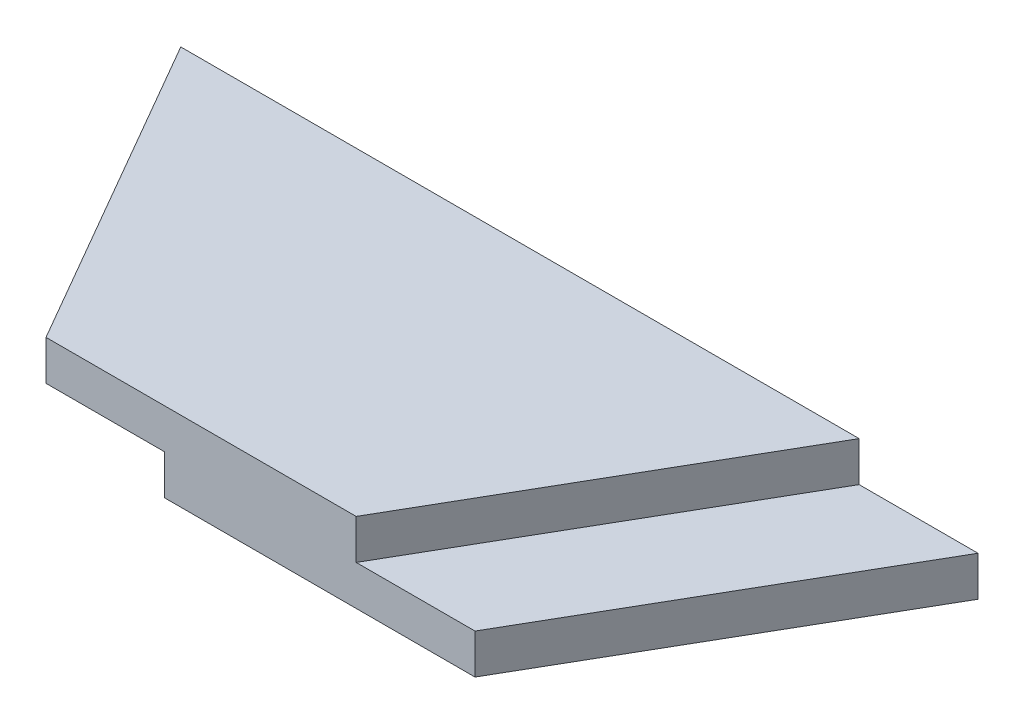
SolidWorks part; units mm, degrees
ref_plane "Спереди" through (0, 0, 0) normal (0, 0, 1) x (1, 0, 0)
ref_plane "Сверху" through (0, 0, 0) normal (0, 1, 0) x (1, 0, 0)
ref_plane "Справа" through (0, 0, 0) normal (1, 0, 0) x (0, 0, -1)
sketch "Эскиз1" plane through (0, 0, 0) normal (1, 0, 0) x (0, 0, -1)
  line L1 (0, 0) -> (80, 0)
  line L2 (0, 0) -> (0, 20)
  line L3 (0, 20) -> (80, 20)
  line L4 (80, 0) -> (80, 20)
extrude "Бобышка-Вытянуть1" add sketch "Эскиз1" along normal blind 200
sketch "Эскиз2" plane through (0, 0, 0) normal (0, -1, 0) x (1, 0, 0)
  line L0 (75.938, 0) -> (29.75, -80)
  line L1 (200, 0) -> (0, 0) construction
  line L2 (200, -80) -> (0, -80) construction
  line L3 (29.75, -80) -> (0, -80)
  line L4 (0, -80) -> (0, 0)
  line L5 (0, 0) -> (75.938, 0)
extrude "Вырез-Вытянуть1" cut sketch "Эскиз2" against normal blind 10
sketch "Эскиз3" plane through (0, 20, 0) normal (0, 1, 0) x (1, 0, 0)
  line L0 (124, 0) -> (170.188, 80)
  line L1 (200, 0) -> (0, 0) construction
  line L3 (200, 80) -> (0, 80) construction
  line L4 (170.188, 80) -> (200, 80)
  line L5 (200, 80) -> (200, 0)
  line L6 (200, 0) -> (124, 0)
extrude "Вырез-Вытянуть2" cut sketch "Эскиз3" against normal blind 10
sketch "Эскиз4" plane through (0, 20, 0) normal (0, 1, 0) x (1, 0, 0)
  line L0 (200, 80) -> (153.812, 0)
  line L1 (124, 0) -> (200, 0) construction
  line L2 (153.812, 0) -> (46.188, 0)
  line L3 (124, 0) -> (0, 0) construction
  line L4 (46.188, 0) -> (0, 80)
  line L5 (0, 80) -> (0, 0) construction
  line L6 (170.188, 80) -> (0, 80) construction
  line L7 (0, 80) -> (200, 80)
extrude "Вырез-Вытянуть4" cut sketch "Эскиз4" against normal through all flip side to cut
